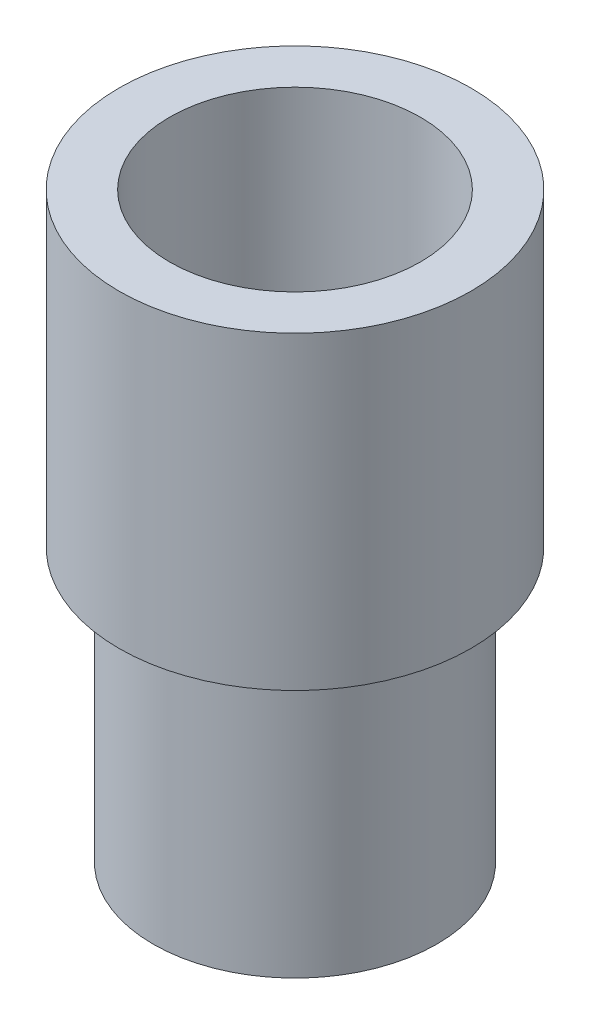
SolidWorks part; units mm, degrees
material "AISI 304"
ref_plane "Front Plane" through (0, 0, 0) normal (0, 0, 1) x (1, 0, 0)
ref_plane "Top Plane" through (0, 0, 0) normal (0, 1, 0) x (1, 0, 0)
ref_plane "Right Plane" through (0, 0, 0) normal (1, 0, 0) x (0, 0, -1)
sketch "Sketch1" plane through (0, 0, 0) normal (0, 0, 1) x (1, 0, 0)
  line L0 (0, 0) -> (0, 65) construction
  line L2 (13.9954, 0) -> (15.8242, 0)
  line L3 (13.9954, 0) -> (13.9954, 30.48)
  line L4 (13.9954, 30.48) -> (15.8242, 30.48)
  line L5 (15.8242, 0) -> (15.8242, 30.48)
  line L6 (13.9954, 30.48) -> (19.6342, 30.48)
  line L7 (13.9954, 30.48) -> (13.9954, 65)
  line L8 (13.9954, 65) -> (19.6342, 65)
  line L9 (19.6342, 30.48) -> (19.6342, 65)
  line L10 (13.9954, 40.48) -> (0, 40.48)
  line L11 (13.9954, 40.48) -> (13.9954, 30.48)
  line L12 (13.9954, 30.48) -> (0, 30.48)
  line L13 (0, 40.48) -> (0, 30.48)
  dimension "D1" = 65
  dimension "D2" = 31.6484
  dimension "D3" = 1.8288
  dimension "D4" = 30.48
  dimension "D5" = 3.81
  dimension "D6" = 10
revolve "Revolve1" add sketch "Sketch1" angle 360 about L0 region at (14.9098, 15.24, 0) region at (16.8148, 47.74, 0) region at (6.9977, 35.48, 0)
